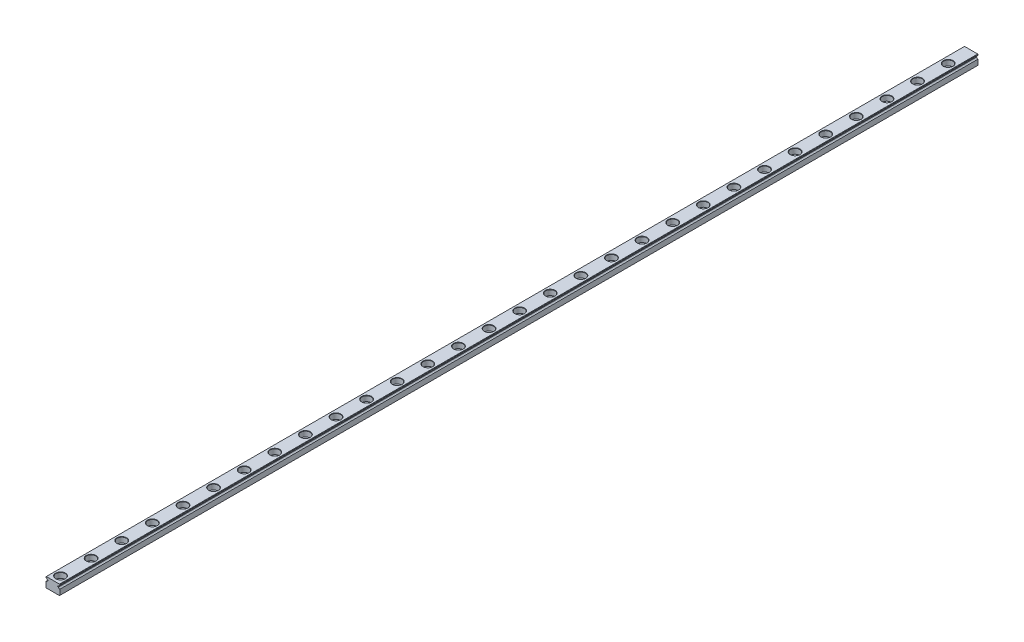
SolidWorks part; units mm, degrees
ref_plane "Спереди" through (0, 0, 0) normal (0, 0, 1) x (1, 0, 0)
ref_plane "Сверху" through (0, 0, 0) normal (0, 1, 0) x (1, 0, 0)
ref_plane "Справа" through (0, 0, 0) normal (1, 0, 0) x (0, 0, -1)
sketch "Sketch1" plane through (0, 0, 0) normal (0, 0, 1) x (1, 0, 0)
  line L0 (0, 0) -> (0, 4.3706) construction
  line L1 (-4.3, -3.25) -> (4.3, -3.25)
  line L2 (-4.5, -3.05) -> (-4.5, 0.455)
  line L3 (-4.3, 3.25) -> (4.3, 3.25)
  line L4 (4.5, -3.05) -> (4.5, 0.455)
  line L5 (-4.5, -3.25) -> (4.5, 3.25) construction
  line L6 (-4.5, 3.25) -> (4.5, -3.25) construction
  line L7 (-4.5, 2.445) -> (-4.5, 3.05)
  line L8 (4.5, 2.445) -> (4.5, 3.05)
  line L9 (-4.5, -3.05) -> (-4.3, -3.25)
  line L10 (4.3, -3.25) -> (4.5, -3.05)
  line L11 (4.3, 3.25) -> (4.5, 3.05)
  line L12 (-4.5, 3.05) -> (-4.3, 3.25)
  line L13 (3.6177, 1.2625) -> (3.1501, 1.2625)
  line L14 (-3.6177, 1.2625) -> (-3.1501, 1.2625)
  line L15 (3.1501, 1.2625) -> (3.1501, 1.7625)
  line L16 (-3.6501, 1.7625) -> (-3.1501, 1.7625)
  line L17 (-3.1501, 1.2625) -> (-3.1501, 1.7625)
  line L18 (3.6501, 1.7625) -> (3.1501, 1.7625)
  arc A0 (-4.5, 2.445) -> (-3.6501, 1.7625) centre (-4.6, 1.45) cw
  arc A1 (4.5, 2.445) -> (3.6501, 1.7625) centre (4.6, 1.45) ccw
  arc A2 (-3.6177, 1.2625) -> (-4.5, 0.455) centre (-4.6, 1.45) cw
  arc A3 (3.6177, 1.2625) -> (4.5, 0.455) centre (4.6, 1.45) ccw
  point P0 (0, 0)
  dimension "D4" = 1
  dimension "D5" = 0.1
  dimension "D1" = 9
  dimension "D2" = 6.5
  dimension "D3" = 1.8
  dimension "D6" = 0.5
  dimension "D7" = 0.5
extrude "Extrude1" add sketch "Sketch1" along normal blind 600
sketch "Sketch2" plane through (0, 3.25, 0) normal (0, 1, 0) x (1, 0, 0)
  line L0 (0, 0) -> (0, -15) construction
  circle A0 centre (0, -15) radius 1.75
  circle A1 centre (0, -15) radius 3
  dimension "D1" = 3.5
  dimension "D2" = 6
  dimension "D3" = 15
extrude "Extrude2" cut sketch "Sketch2" against normal up to next contours A0 region at (0, 3.25, 15)
extrude "Extrude4" cut sketch "Sketch" against normal blind 3.5
sketch "Sketch" plane through (0, 3.25, 0) normal (0, 1, 0) x (1, 0, 0) same geometry as "Sketch2"
chamfer "Chamfer1" distance 0.2 angle 45 2 edges at (0, -3.25, 16.75) (0, 3.25, 18)
pattern_linear "LPattern1" count 30 spacing 20 along (0, 0, 1) of "Extrude4", "Chamfer1", "Extrude2"
